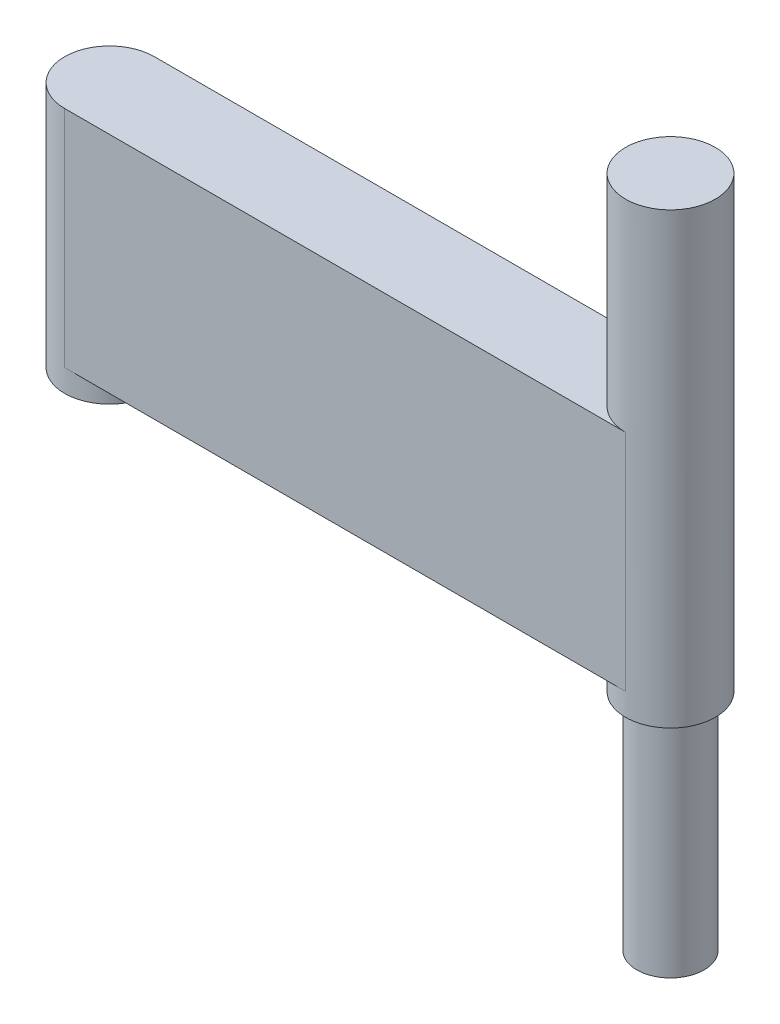
SolidWorks part; units mm, degrees
ref_plane "Front Plane" through (0, 0, 0) normal (0, 0, 1) x (1, 0, 0)
ref_plane "Top Plane" through (0, 0, 0) normal (0, 1, 0) x (1, 0, 0)
ref_plane "Right Plane" through (0, 0, 0) normal (1, 0, 0) x (0, 0, -1)
sketch "Sketch1" plane through (0, 0, 0) normal (0, 1, 0) x (1, 0, 0)
  circle A0 centre (0, 0) radius 20
extrude "Boss-Extrude1" add sketch "Sketch1" along normal blind 10
sketch "Sketch2" plane through (0, 10, 0) normal (0, 1, 0) x (1, 0, 0)
  line L1 (0, -20) -> (250, -20)
  line L2 (0, 20) -> (250, 20)
  arc A0 (0, 20) -> (0, -20) centre (0, 0) ccw
  arc A1 (250, -20) -> (250, 20) centre (250, 0) ccw
  dimension "D1" = 250
extrude "Boss-Extrude2" add sketch "Sketch2" along normal blind 100
sketch "Sketch3" plane through (0, 10, 0) normal (0, -1, 0) x (1, 0, 0)
  circle A0 centre (250, 0) radius 20
extrude "Boss-Extrude3" add sketch "Sketch3" along normal blind 10
sketch "Sketch6" plane through (0, 110, 0) normal (0, 1, 0) x (1, 0, 0)
  circle A0 centre (250, 0) radius 20
extrude "Boss-Extrude5" add sketch "Sketch6" along normal blind 90
sketch "Sketch9" plane through (0, 0, 0) normal (0, -1, 0) x (1, 0, 0)
  circle A0 centre (250, 0) radius 15
extrude "Boss-Extrude6" add sketch "Sketch9" along normal blind 100
